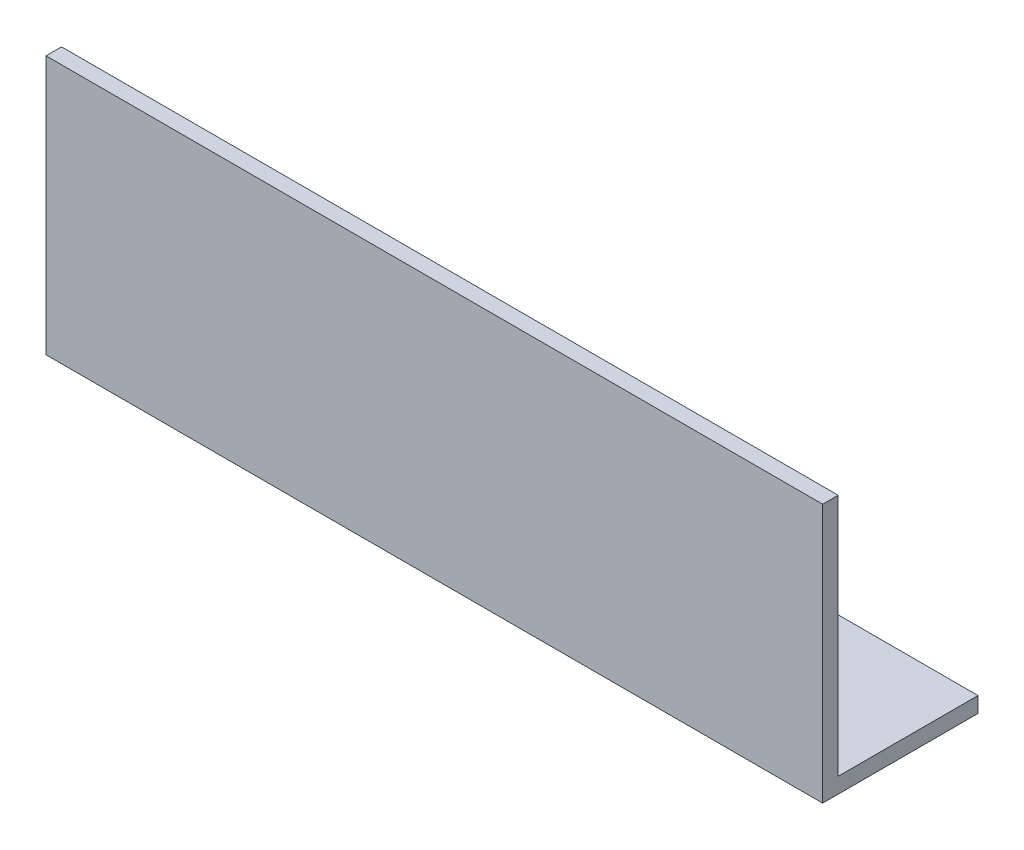
SolidWorks part; units mm, degrees
ref_plane "Спереди" through (0, 0, 0) normal (0, 0, 1) x (1, 0, 0)
ref_plane "Сверху" through (0, 0, 0) normal (0, 1, 0) x (1, 0, 0)
ref_plane "Справа" through (0, 0, 0) normal (1, 0, 0) x (0, 0, -1)
sketch "Эскиз1" plane through (0, 0, 0) normal (1, 0, 0) x (0, 0, -1)
  line L0 (0, 0) -> (0, 50)
  line L1 (0, 0) -> (30, 0)
extrude "Вытянуть-Тонкостенный1" add sketch "Эскиз1" along normal blind 150 thin thin type one direction reverse wall 3
